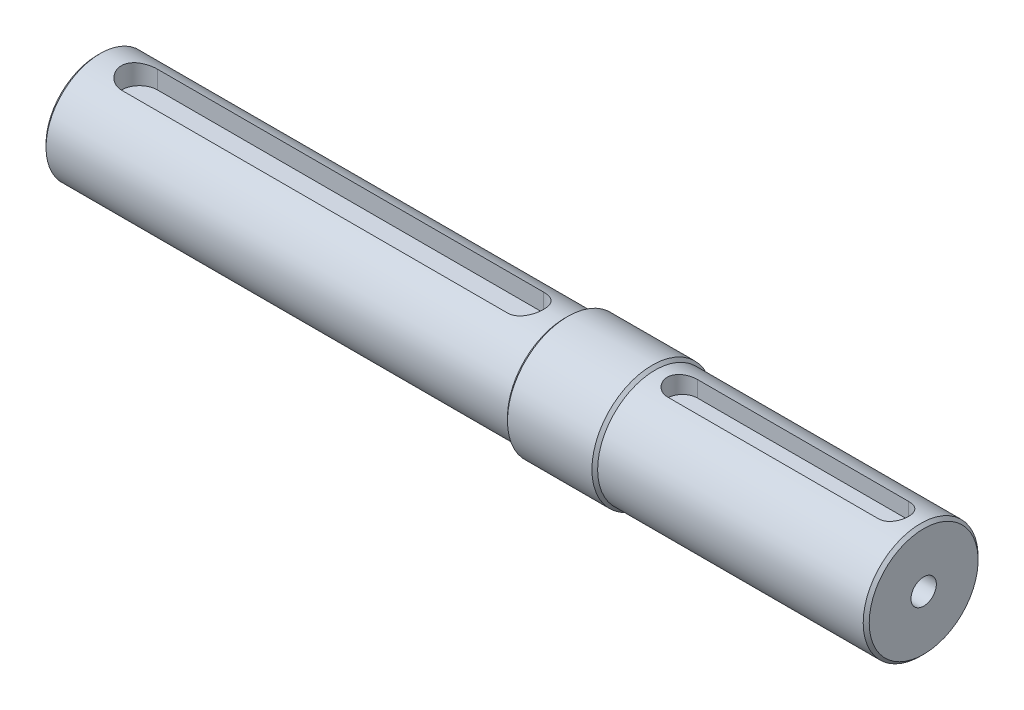
SolidWorks part; units mm, degrees
material "1.0503 (C45)"
ref_plane "前视基准面" through (0, 0, 0) normal (0, 0, 1) x (1, 0, 0)
ref_plane "上视基准面" through (0, 0, 0) normal (0, 1, 0) x (1, 0, 0)
ref_plane "右视基准面" through (0, 0, 0) normal (1, 0, 0) x (0, 0, -1)
sketch "轴轴向刨面" plane through (0, 0, 0) normal (0, 0, 1) x (1, 0, 0)
  line L3 (0, 9) -> (77.5, 9)
  line L4 (77.5, 9) -> (77.5, 10)
  line L5 (77.5, 10) -> (92.5, 10)
  line L6 (92.5, 10) -> (92.5, 9.525)
  line L7 (92.5, 9.525) -> (137, 9.525)
  line L20 (-7.7673, 0) -> (202.2389, 0) construction
  line L21 (0, 9) -> (0, 0)
  line L22 (137, 9.525) -> (137, 0)
  line L23 (0, 0) -> (137, 0)
  dimension "D1" = 44.5
  dimension "D2" = 18
  dimension "D3" = 77.5
  dimension "D4" = 15
  dimension "D5" = 20
  dimension "D6" = 19.05
revolve "旋转轴" add sketch "轴轴向刨面" angle 360 about L23
ref_plane "9mm键槽面" through (0, 9, 0) normal (0, 1, 0) x (1, 0, 0)
sketch "草图24" plane through (0, 9, 0) normal (0, 1, 0) x (1, 0, 0)
  line L0 (7, 0) -> (71, 0) construction
  line L3 (7, 3) -> (71, 3)
  line L4 (7, -3) -> (71, -3)
  line L7 (0, 9) -> (0, -9) construction
  line L9 (77.5, 10) -> (77.5, -10) construction
  arc A2 (7, 3) -> (7, -3) centre (7, 0) ccw
  arc A3 (71, -3) -> (71, 3) centre (71, 0) ccw
  point P2 (39, 0)
  point P3 (4, 0)
  point P8 (74, 0)
  dimension "D2" = 70
  dimension "D1" = 4
  dimension "D3" = 6
  dimension "D4" = 3.5
extrude "切除-拉伸11" cut sketch "草图24" against normal blind 3.5
ref_plane "9.52mm键槽面" through (0, 9.525, 0) normal (0, 1, 0) x (1, 0, 0)
sketch "草图25" plane through (0, 9.525, 0) normal (0, 1, 0) x (1, 0, 0)
  line L0 (97, 0) -> (132, 0) construction
  line L1 (92.5, 0) -> (137, 0) construction
  line L2 (97, 2.5) -> (132, 2.5)
  line L3 (97, -2.5) -> (132, -2.5)
  line L7 (92.5, -10) -> (92.5, 10) construction
  line L8 (137, -9.525) -> (137, 9.525) construction
  arc A0 (97, 2.5) -> (97, -2.5) centre (97, 0) ccw
  arc A1 (132, -2.5) -> (132, 2.5) centre (132, 0) ccw
  point P5 (114.5, 0)
  point P12 (94.5, 0)
  point P13 (134.5, 0)
  dimension "D2" = 5
  dimension "D1" = 4.5
  dimension "D3" = 40
  dimension "D4" = 35
  dimension "D5" = 5
extrude "切除-拉伸12" cut sketch "草图25" against normal blind 3
hole_wizard "M5 螺纹孔 减速机" positions "草图38" profile "草图37" tap size "M5" standard "GB"
sketch "草图38" plane through (0, 0, 0) normal (1, 0, 0) x (0, 0, -1)
  point P0 (0, 0)
sketch "草图37" plane through (0, 0, 0) normal (0, 1, 0) x (0, 0, 1)
  line L0 (0, 0) -> (0, 29.2618)
  line L1 (0, 29.2618) -> (2.1, 28)
  line L2 (2.1, 28) -> (2.1, 0)
  line L5 (2.1, 0) -> (0, 0)
  line L10 (0, 29.2618) -> (-2.1, 28) construction
  line L11 (0, -6.35) -> (0, 107.95) construction
  dimension "螺纹孔钻头直径" = 4.2
  dimension "螺纹孔钻头深度" = 28
  dimension "导头角度" = 118
cosmetic thread "孔螺蚊线1" parameters "D1"=24, "D2"=5
hole_wizard "M5 螺纹孔 轮毂固定" positions "草图42" profile "草图43" tap size "M5" standard "GB"
sketch "草图42" plane through (137, 0, 0) normal (1, 0, 0) x (0, 0, -1)
  point P0 (0, 0)
cosmetic thread "孔螺蚊线2" parameters "D1"=24, "D2"=5
sketch "草图43" plane through (137, 0, 0) normal (0, 1, 0) x (0, 0, -1)
  line L0 (0, 0) -> (0, 29.2618)
  line L1 (0, 29.2618) -> (2.1, 28)
  line L2 (2.1, 28) -> (2.1, 0)
  line L5 (2.1, 0) -> (0, 0)
  line L10 (0, 29.2618) -> (-2.1, 28) construction
  line L11 (0, -6.35) -> (0, 107.95) construction
  dimension "螺纹孔钻头直径" = 4.2
  dimension "螺纹孔钻头深度" = 28
  dimension "导头角度" = 118
chamfer "倒角3" distance 0.5 angle 45 4 edges at (137, 0, 9.525) (92.5, 0, 10) (77.5, 0, 10) (0, 0, 9)
